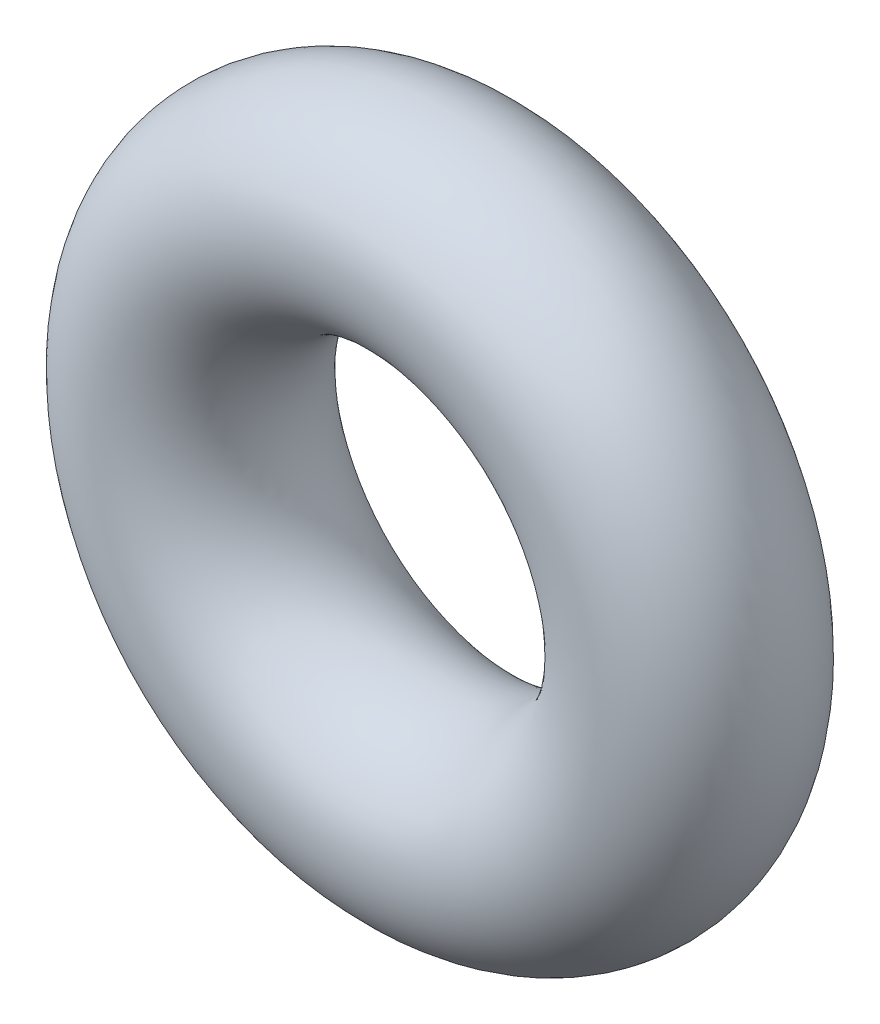
SolidWorks part; units mm, degrees
ref_plane "Front" through (0, 0, 0) normal (0, 0, 1) x (1, 0, 0)
ref_plane "Top" through (0, 0, 0) normal (0, 1, 0) x (1, 0, 0)
ref_plane "Right" through (0, 0, 0) normal (1, 0, 0) x (0, 0, -1)
sketch "Sketch1" plane through (0, 0, 0) normal (1, 0, 0) x (0, -1, 0)
  line L0 (0, -0.889) -> (0, 0.889) construction
  line L2 (-3.3668, 0) -> (3.3668, 0) construction
  line L3 (-1.2827, 0) -> (1.2827, 0) construction
  circle A0 centre (2.1717, 0) radius 0.889
  point P9 (1.2827, 0)
  point P10 (3.0607, 0)
  point P13 (2.1717, 0.889)
  point P14 (2.1717, -0.889)
  dimension "Width" = 1.778
  dimension "ID" = 2.5654
revolve "Revolve1" add sketch "Sketch1" angle 360 about L0
ref_axis "Axis1" through (0, 0, 0.9779) along (0, 0, -1)
